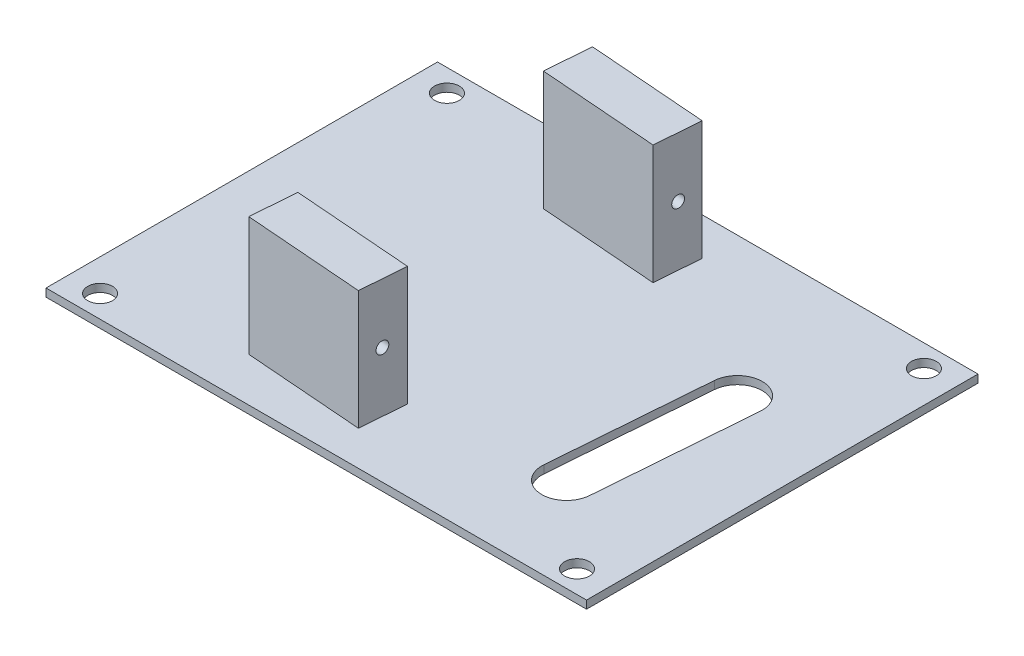
SolidWorks part; units mm, degrees
ref_plane "Ön Düzlem" through (0, 0, 0) normal (0, 0, 1) x (1, 0, 0)
ref_plane "Üst Düzlem" through (0, 0, 0) normal (0, 1, 0) x (1, 0, 0)
ref_plane "Sağ Düzlem" through (0, 0, 0) normal (1, 0, 0) x (0, 0, -1)
sketch "Çizim1" plane through (0, 0, 0) normal (0, 1, 0) x (1, 0, 0)
  line L1 (0, 0) -> (54.4, 0)
  line L2 (0, 0) -> (0, 39.4)
  line L3 (0, 39.4) -> (54.4, 39.4)
  line L4 (54.4, 0) -> (54.4, 39.4)
  dimension "D1" = 54.4
  dimension "D2" = 39.4
extrude "Yükseklik-Ekstrüzyon1" add sketch "Çizim1" along normal blind 0.8
sketch "Çizim2" plane through (0, 0.8, 0) normal (0, 1, 0) x (1, 0, 0)
  line L0 (3.2, 2.245) -> (51.2, 37.155) construction
  line L1 (3.2, 37.155) -> (51.2, 2.245) construction
  line L2 (27.2, 39.4) -> (27.2, 0) construction
  line L3 (54.4, 39.4) -> (0, 39.4) construction
  line L4 (0, 0) -> (54.4, 0) construction
  circle A4 centre (3.2, 37.155) radius 1.25
  circle A5 centre (51.2, 37.155) radius 1.25
  circle A6 centre (3.2, 2.245) radius 1.25
  circle A7 centre (51.2, 2.245) radius 1.25
  point P10 (27.2, 19.7)
  dimension "D1" = 48
  dimension "D3" = 2.5
  dimension "D2" = 34.91
extrude "Kes-Ekstrüzyon1" cut sketch "Çizim2" against normal through all
sketch "Çizim3" plane through (0, 0.8, 0) normal (0, 1, 0) x (1, 0, 0)
  line L0 (0, 0) -> (54.4, 39.4) construction
  line L1 (42.4041, 2.371) -> (44.8969, 34.4743) construction
  line L2 (42.4041, 2.371) -> (9.5031, 4.9257) construction
  line L3 (44.8969, 34.4743) -> (11.9959, 37.029) construction
  line L4 (9.5031, 4.9257) -> (11.9959, 37.029) construction
  line L5 (54.4, 39.4) -> (0, 39.4) construction
  line L6 (10.7495, 20.9773) -> (43.6505, 18.4227) construction
  line L8 (9.5031, 4.9257) -> (9.8592, 9.5119)
  line L9 (9.5031, 4.9257) -> (27.9476, 3.4935)
  line L10 (9.8592, 9.5119) -> (28.3037, 8.0797)
  line L11 (27.9476, 3.4935) -> (28.3037, 8.0797)
  line L12 (11.9959, 37.029) -> (11.6398, 32.4428)
  line L13 (11.9959, 37.029) -> (30.4404, 35.5969)
  line L14 (11.6398, 32.4428) -> (30.0843, 31.0107)
  line L15 (30.4404, 35.5969) -> (30.0843, 31.0107)
  line L16 (18.4764, 36.5258) -> (18.1203, 31.9396)
  line L17 (16.3397, 9.0087) -> (15.9836, 4.4225)
  line L18 (44.192, 25.3971) -> (42.9534, 9.4451) construction
  line L19 (46.6845, 25.2036) -> (45.4459, 9.2516)
  line L20 (41.6995, 25.5907) -> (40.4609, 9.6387)
  arc A0 (46.6845, 25.2036) -> (41.6995, 25.5907) centre (44.192, 25.3971) ccw
  arc A1 (40.4609, 9.6387) -> (45.4459, 9.2516) centre (42.9534, 9.4451) ccw
  point P4 (27.2, 19.7)
  point P9 (41.5013, 1.498)
  point P10 (43.3762, 16.4474)
  point P25 (43.5727, 17.4211)
  point P30 (11.5585, 36.4696)
  point P33 (0, 0)
  point P34 (0, 0)
  point P35 (0, 0)
  point P36 (40.7116, 12.8151)
  dimension "D1" = 4.44
  dimension "D2" = 30.5
  dimension "D3" = 32.2
  dimension "D4" = 23
  dimension "D5" = 18.5
  dimension "D6" = 12
  dimension "D7" = 5
  dimension "D8" = 16
  dimension "D9" = 5.42
extrude "Yükseklik-Ekstrüzyon2" add sketch "Çizim3" along normal blind 12 contours L10 L17 L9 L11 | L13 L16 L14 L15 region at (22.1437, 0.8, -6.2511) region at (24.2803, 0.8, -33.7682)
extrude "Kes-Ekstrüzyon2" cut sketch "Çizim3<3>" against normal through all contours L20 A1 L19 A0 region at (43.5727, 0.8, -17.4211)
sketch "Çizim3<3>" plane through (0, 0.8, 0) normal (0, 1, 0) x (1, 0, 0) same geometry as "Çizim3"
sketch "Çizim4" plane through (27.5105, 0, 2.1361) normal (0.997, 0, 0.0774) x (0.0774, 0, -0.997)
  line L0 (5.6466, 6.8) -> (37.8466, 6.8) construction
  line L1 (5.6466, 12.8) -> (5.6466, 0.8) construction
  line L2 (37.8466, 12.8) -> (37.8466, 0.8) construction
  line L3 (21.7466, 0.8) -> (21.7466, 6.8) construction
  circle A0 centre (7.8966, 6.8) radius 0.6
  circle A1 centre (35.5966, 6.8) radius 0.6
  dimension "D1" = 27.7
  dimension "D2" = 1.2
extrude "Kes-Ekstrüzyon3" cut sketch "Çizim4" against normal blind 6
